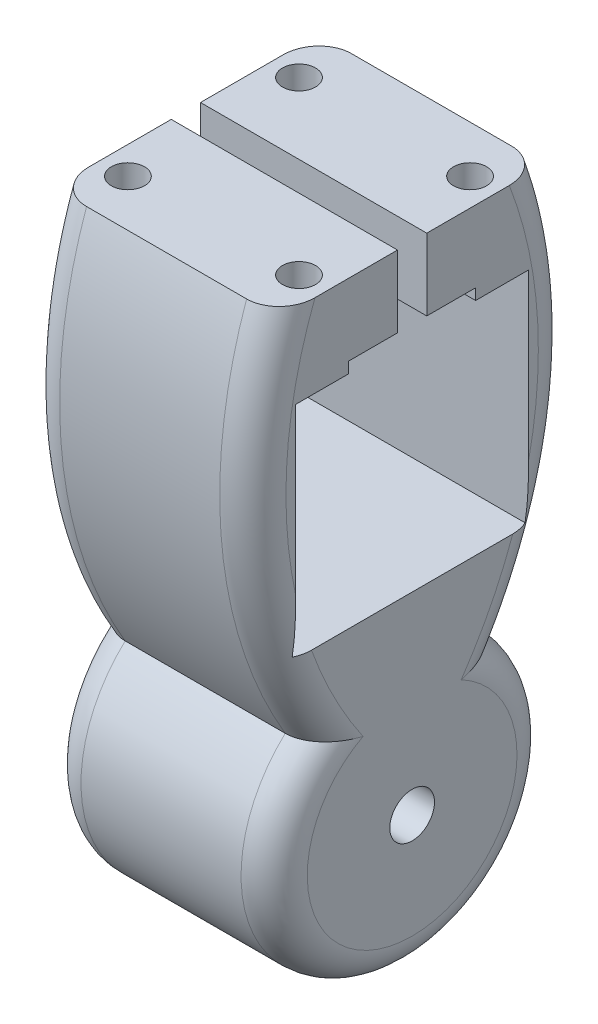
SolidWorks part; units mm, degrees
ref_plane "Front Plane" through (0, 0, 0) normal (0, 0, 1) x (1, 0, 0)
ref_plane "Top Plane" through (0, 0, 0) normal (0, 1, 0) x (1, 0, 0)
ref_plane "Right Plane" through (0, 0, 0) normal (1, 0, 0) x (0, 0, -1)
sketch "Sketch1" plane through (0, 0, 0) normal (1, 0, 0) x (0, 0, -1)
  line L0 (0, 0) -> (0, 86.1529) construction
  line L1 (-24, 90) -> (24, 90)
  circle A0 centre (0, 0) radius 25
  arc A1 (24, 90) -> (17, 18.3303) centre (-56.1328, 61.6499) cw
  arc A2 (-24, 90) -> (-17, 18.3303) centre (56.1328, 61.6499) ccw
  dimension "D1" = 50
  dimension "D3" = 85
  dimension "D2" = 24
  dimension "D4" = 90
  dimension "D5" = 17
extrude "Boss-Extrude1" add sketch "Sketch1" along normal blind 41 contours A0 L0 L1 | L0 A0 L1 | A0 region at (0, 57.2311, 0) region at (0, 0, 0)
sketch "Sketch2" plane through (0, 0, 0) normal (1, 0, 0) x (0, 0, -1)
  circle A0 centre (0, 0) radius 4.05
  circle A1 centre (0, 0) radius 11
  dimension "D1" = 8.1
  dimension "D2" = 22
extrude "Cut-Extrude1" cut sketch "Sketch2" along normal up to next contours A0
sketch "Sketch3" plane through (0, 0, 0) normal (1, 0, 0) x (0, 0, -1)
  line L0 (-24, 90) -> (24, 90) construction
  line L1 (21.1, 35) -> (-21.1, 35)
  line L2 (21.1, 35) -> (21.1, 75)
  line L3 (21.1, 75) -> (-21.1, 75)
  line L4 (-21.1, 35) -> (-21.1, 75)
  line L5 (21.1, 35) -> (-21.1, 75) construction
  line L6 (21.1, 75) -> (-21.1, 35) construction
  line L7 (11.5, 77) -> (-11.5, 77)
  line L8 (11.5, 77) -> (11.5, 73)
  line L9 (11.5, 73) -> (-11.5, 73)
  line L10 (-11.5, 77) -> (-11.5, 73)
  line L11 (11.5, 77) -> (-11.5, 73) construction
  line L12 (11.5, 73) -> (-11.5, 77) construction
  line L17 (2.65, 64) -> (-2.65, 64)
  line L18 (2.65, 64) -> (2.65, 90)
  line L19 (2.65, 90) -> (-2.65, 90)
  line L20 (-2.65, 64) -> (-2.65, 90)
  line L21 (2.65, 64) -> (-2.65, 90) construction
  line L22 (2.65, 90) -> (-2.65, 64) construction
  point P0 (0, 55)
  point P5 (0, 75)
  point P11 (0, 77)
  dimension "D1" = 40
  dimension "D2" = 42.2
  dimension "D3" = 2
  dimension "D4" = 23
  dimension "D5" = 5.3
  dimension "D6" = 55
extrude "Cut-Extrude2" cut sketch "Sketch3" along normal blind 42.2 contours L10 L3 L4 L1 L2 L8 L9 | L18 L3 L8 L7 | L20 L3 L18 L7 | L3 L20 L7 L10 | L20 L7 L18 L19 | L8 L7 L10 L9 | L18 L17 L20 L19 region at (0, 54.0479, 0) region at (0, 76, -7.075) region at (0, 76, 7.075) region at (0, 76, 0) region at (0, 83.5, 0)
sketch "Sketch4" plane through (0, 0, 0) normal (0, 1, 0) x (1, 0, 0)
  line L1 (36, -15.5) -> (5, -15.5) construction
  line L2 (36, -15.5) -> (36, 15.5) construction
  line L3 (36, 15.5) -> (5, 15.5) construction
  line L4 (5, -15.5) -> (5, 15.5) construction
  line L5 (36, -15.5) -> (5, 15.5) construction
  line L6 (36, 15.5) -> (5, -15.5) construction
  circle A0 centre (36, -15.5) radius 1.55
  circle A1 centre (5, -15.5) radius 1.55
  circle A2 centre (5, 15.5) radius 1.55
  circle A3 centre (36, 15.5) radius 1.55
  circle A4 centre (36, -15.5) radius 3
  circle A5 centre (5, -15.5) radius 3
  circle A6 centre (5, 15.5) radius 3
  circle A7 centre (36, 15.5) radius 3
  point P0 (20.5, 0)
  dimension "D1" = 3.1
  dimension "D5" = 6
  dimension "D2" = 31
  dimension "D3" = 31
  dimension "D4" = 20.5
extrude "Cut-Extrude3" cut sketch "Sketch4" against normal up to next from surface contours A0 | A1 | A2 | A3 starting at face at (20.5, 90, 13.325)
extrude "Cut-Extrude4" cut sketch "Sketch4<3>" against normal blind 10 from surface contours A7 | A4 | A5 | A6 starting at face at (36, 90, -13.95)
sketch "Sketch4<3>" plane through (0, 0, 0) normal (0, 1, 0) x (1, 0, 0) same geometry as "Sketch4"
sketch "Sketch5" plane through (0, 0, 0) normal (1, 0, 0) x (0, 0, -1)
  circle A0 centre (0, 0) radius 15.05
  dimension "D1" = 30.1
extrude "Cut-Extrude5" cut sketch "Sketch5" along normal blind 7.1
fillet "Fillet1" radius 6 6 edges at (0, -25, 0) (0, 53.3872, -28.4646) (0, 53.3872, 28.4646) (41, -25, 0) (41, 53.3872, -28.4646) (41, 53.3872, 28.4646)
equation "\"bottom dia\"=50"
equation "\"D1@Sketch1\"=\"bottom dia\""
equation "\"arm width\"= 41"
equation "\"D1@Boss-Extrude1\"= \"arm width\""
equation "\"bearing bore\"= 8.1"
equation "\"stepper motor hole dist\"= 31"
equation "\"stepper motor width\"= 42.2"
equation "\"arm top width\"=24"
equation "\"D2@Sketch1\"=\"arm top width\""
equation "\"dist to attachment\"=17"
equation "\"arm radius\"=85"
equation "\"D3@Sketch1\"=\"arm radius\""
equation "\"arm length\"=90"
equation "\"D4@Sketch1\"=\"arm length\""
equation "\"D1@Sketch2\"=\"bearing bore\""
equation "\"bearing OD\"=22"
equation "\"D2@Sketch2\"=\"bearing OD\""
equation "\"stepper motor height\"=40"
equation "\"D1@Sketch3\"=\"stepper motor height\""
equation "\"dist to stepper motor\"=55"
equation "\"D6@Sketch3\"=\"dist to stepper motor\""
equation "\"D2@Sketch3\"=\"stepper motor width\""
equation "\"D2@Sketch4\"=\"stepper motor hole dist\""
equation "\"M3 hole\"=3.1"
equation "\"D1@Sketch4\"=\"M3 hole\""
equation "\"D4@Sketch4\"=\"arm width\"/2"
equation "\"D3@Sketch4\"=\"stepper motor hole dist\""
equation "\"M3 head size\"=6"
equation "\"D5@Sketch4\"=\"M3 head size\""
equation "\"gear extension depth\" = 7.1"
equation "\"D1@Cut-Extrude5\"=\"gear extension depth\""
equation "\"gear extension OD\"= 30.1"
equation "\"D1@Sketch5\"=\"gear extension OD\""
